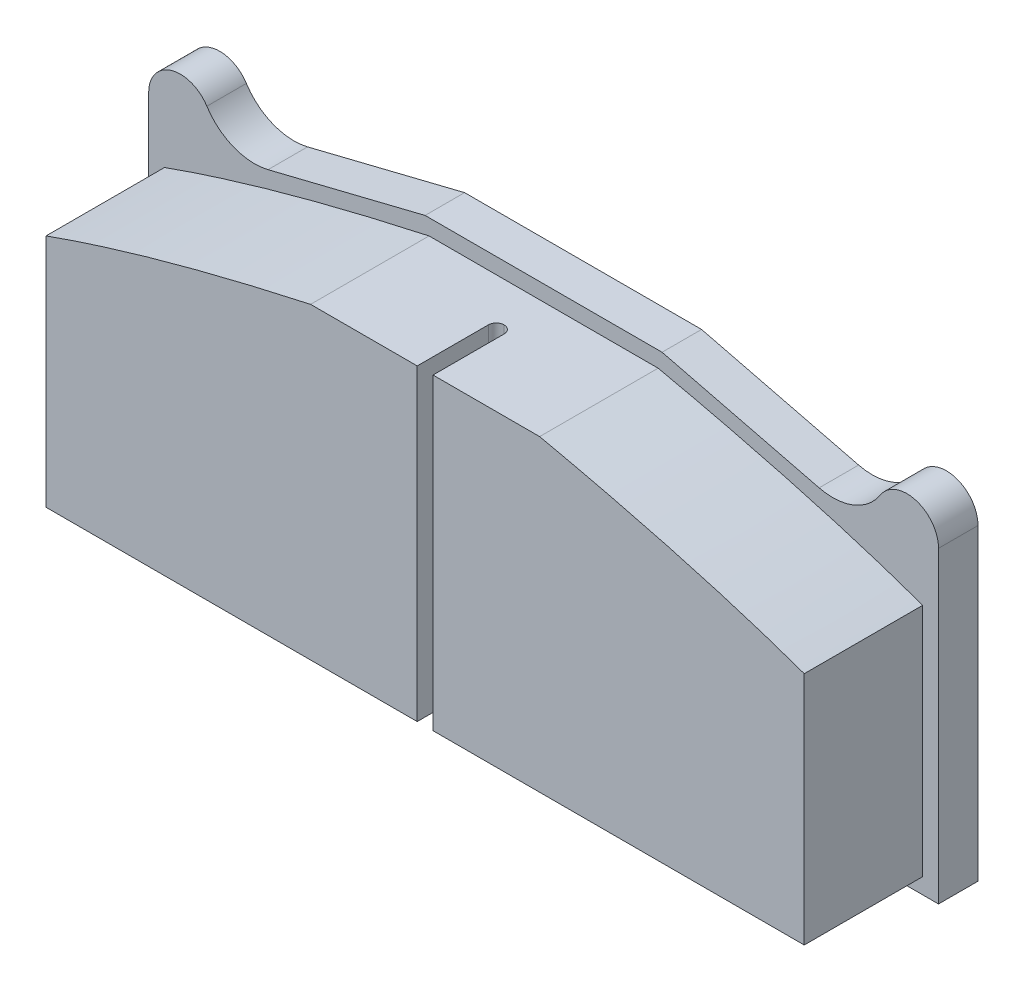
SolidWorks part; units mm, degrees
ref_plane "Front Plane" through (0, 0, 0) normal (0, 0, 1) x (1, 0, 0)
ref_plane "Top Plane" through (0, 0, 0) normal (0, 1, 0) x (1, 0, 0)
ref_plane "Right Plane" through (0, 0, 0) normal (1, 0, 0) x (0, 0, -1)
sketch "Sketch1" plane through (0, 0, 0) normal (0, 0, 1) x (1, 0, 0)
  line L0 (15, 21.4218) -> (34.8875, 16.4959)
  line L1 (15, 21.4218) -> (-15, 21.4218)
  line L2 (50, 17.4218) -> (50, -21.5782)
  line L3 (50, -21.5782) -> (-50, -21.5782)
  line L7 (0, 40.0104) -> (0, -39.8965) construction
  line L8 (-50, 17.4218) -> (-50, -21.5782)
  line L9 (-15, 21.4218) -> (-34.8875, 16.4959)
  line L10 (48, 10.1761) -> (48, -19.5782)
  line L11 (48, -19.5782) -> (-48, -19.5782)
  line L13 (48, 19.6921) -> (-48, -19.5782) construction
  line L14 (48, -19.5782) -> (-48, 19.6921) construction
  line L15 (-14.5, 19.4218) -> (14.5, 19.4218)
  line L16 (-48, 10.1761) -> (-48, -19.5782)
  line L17 (-14.5, 19.4218) -> (-34.3276, 15.0953) construction
  line L18 (14.5, 19.4218) -> (34.3276, 15.0953) construction
  line L19 (34.3276, 15.0953) -> (48, 10.1761) construction
  line L20 (-34.3276, 15.0953) -> (-48, 10.1761) construction
  arc A0 (50, 17.4218) -> (42.6324, 19.5803) centre (46, 17.4218) ccw
  arc A1 (34.8875, 16.4959) -> (42.6324, 19.5803) centre (36.6079, 23.4419) ccw
  arc A2 (-50, 17.4218) -> (-42.6324, 19.5803) centre (-46, 17.4218) cw
  arc A3 (-34.8875, 16.4959) -> (-42.6324, 19.5803) centre (-36.6079, 23.4419) cw
  spline S0 degree 2 poles (14.5, 19.4218) (34.3276, 15.0953) (48, 10.1761) knots 0 0 0 1 1 1
  spline S1 degree 2 poles (-14.5, 19.4218) (-34.3276, 15.0953) (-48, 10.1761) knots 0 0 0 1 1 1
  point P0 (0, 0)
  point P4 (0, -21.5782)
  point P12 (0, 0.0569)
  point P22 (0, 21.4218)
  point P26 (0, -19.5782)
  point P32 (0, 19.4218)
  dimension "D2" = 4
  dimension "D1" = 30
  dimension "D3" = 2
  dimension "D5" = 100
  dimension "D6" = 2
  dimension "D7" = 39
ref_plane "Plane2" through (0, 0, 5) normal (0, 0, 1) x (1, 0, 0)
sketch "Sketch2" plane through (0, 0, 5) normal (0, 0, 1) x (1, 0, 0)
  line L0 (-14.5, 19.4218) -> (14.5, 19.4218) construction
  line L1 (48, 10.1761) -> (48, -19.5782) construction
  line L2 (48, -19.5782) -> (-48, -19.5782) construction
  line L3 (-48, 10.1761) -> (-48, -19.5782) construction
  line L4 (-14.5, 19.4218) -> (14.5, 19.4218)
  line L5 (48, 10.1761) -> (48, -19.5782)
  line L6 (48, -19.5782) -> (-48, -19.5782)
  line L7 (-48, 10.1761) -> (-48, -19.5782)
  parabola Q0 (14.5, 19.4218) -> (48, 10.1761) focus (72.1109, -14.0004) apex (78.3133, -13.403) construction
  parabola Q1 (-14.5, 19.4218) -> (-48, 10.1761) focus (-72.1109, -14.0004) apex (-78.3133, -13.403) construction
  parabola Q2 (14.5, 19.4218) -> (48, 10.1761) focus (72.1109, -14.0004) apex (78.3133, -13.403)
  parabola Q3 (-14.5, 19.4218) -> (-48, 10.1761) focus (-72.1109, -14.0004) apex (-78.3133, -13.403)
extrude "Boss-Extrude5" add sketch "Sketch2" along normal blind 15
extrude "Boss-Extrude6" add sketch "Sketch1" along normal blind 5 contours L15 S1 L16 L11 L10 S0 | L9 A3 A2 L8 L3 L2 A0 A1 L0 L1 S1 L15 S0 L10 L11 L16 region at (24.682, 17.9023, 0) region at (0, -1.4375, 0)
sketch "Sketch3" plane through (0, 0, 20) normal (0, 0, 1) x (1, 0, 0)
  line L0 (0, 26.6623) -> (0, -28.8756) construction
  line L1 (-48, -19.5782) -> (48, -19.5782) construction
  line L2 (1, 19.5782) -> (-1, 19.5782)
  line L3 (1, 19.5782) -> (1, -19.5782)
  line L4 (1, -19.5782) -> (-1, -19.5782)
  line L5 (-1, 19.5782) -> (-1, -19.5782)
  line L6 (1, 19.5782) -> (-1, -19.5782) construction
  line L7 (1, -19.5782) -> (-1, 19.5782) construction
  point P3 (0, 0)
  dimension "D1" = 2
extrude "Cut-Extrude1" cut sketch "Sketch3" against normal blind 10
fillet "Fillet2" radius 1 2 edges at (1, -0.0782, 10) (-1, -0.0782, 10)
